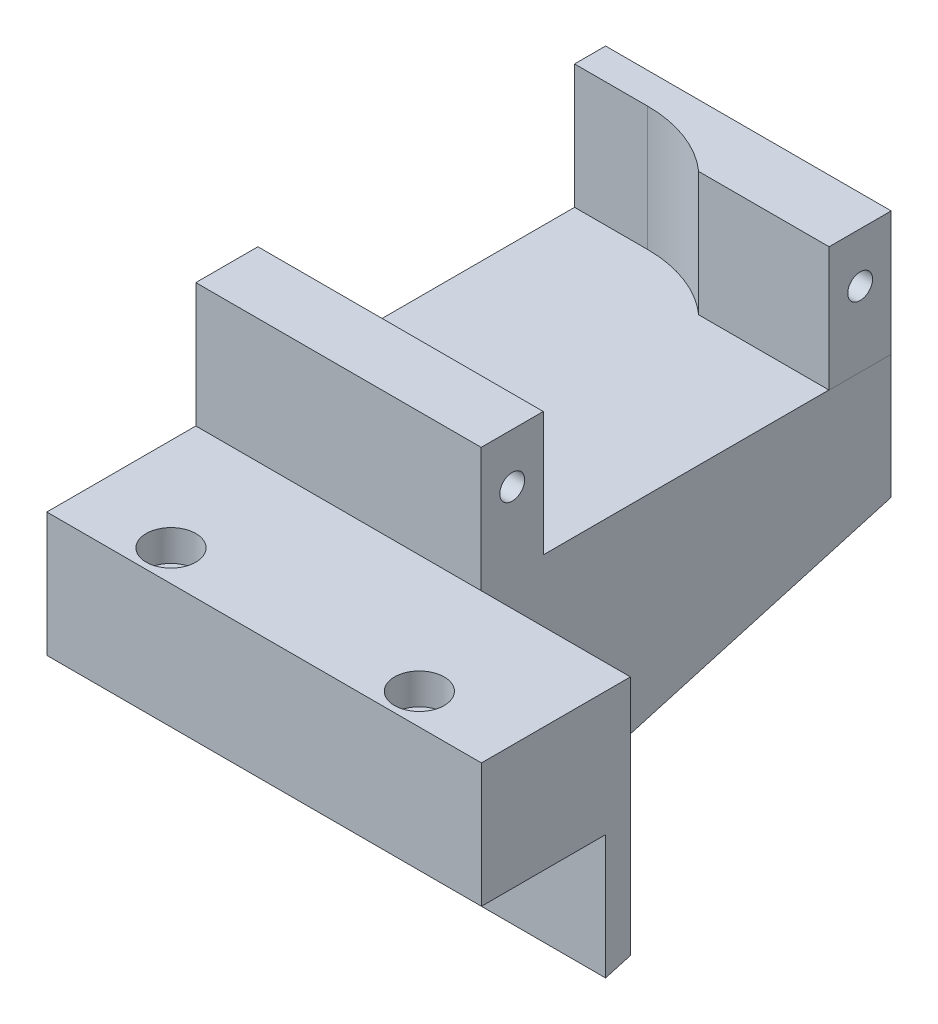
SolidWorks part; units mm, degrees
ref_plane "Front Plane" through (0, 0, 0) normal (0, 0, 1) x (1, 0, 0)
ref_plane "Top Plane" through (0, 0, 0) normal (0, 1, 0) x (1, 0, 0)
ref_plane "Right Plane" through (0, 0, 0) normal (1, 0, 0) x (0, 0, -1)
sketch "Sketch1" plane through (0, 0, 0) normal (0, 1, 0) x (1, 0, 0)
  line L1 (-17.5, 40) -> (17.5, 40)
  line L2 (-17.5, 40) -> (-17.5, -5)
  line L3 (-17.5, -5) -> (17.5, -5)
  line L4 (17.5, 40) -> (17.5, -5)
  circle A0 centre (-10, -2.5) radius 1.1
  circle A1 centre (10, -2.5) radius 1.1
  point P0 (0, 0)
  point P9 (0, 0)
  dimension "D1" = 20
  dimension "D2" = 2.5
extrude "Boss-Extrude1" add sketch "Sketch1" along normal blind 10
sketch "Sketch5" plane through (0, 0, 0) normal (0, -1, 0) x (1, 0, 0)
  line L0 (17.5, 5) -> (17.5, -40) construction
  line L1 (-17.5, -40) -> (17.5, -40)
  line L2 (-17.5, -40) -> (-17.5, -5)
  line L3 (-17.5, -5) -> (17.5, -5)
  line L4 (17.5, -40) -> (17.5, -5)
extrude "Boss-Extrude3" add sketch "Sketch5" along normal blind 10
sketch "Sketch6" plane through (17.5, 0, 0) normal (1, 0, 0) x (0, 0, -1)
  line L0 (5, -10) -> (40, 0)
  line L1 (40, 10) -> (40, -10) construction
  line L2 (40, 0) -> (40, -10)
  line L3 (40, -10) -> (5, -10)
extrude "Cut-Extrude1" cut sketch "Sketch6" against normal blind 50
sketch "Sketch7" plane through (0, 10, 0) normal (0, 1, 0) x (1, 0, 0)
  line L1 (-17.5, 40) -> (5.5, 40)
  line L2 (-17.5, 40) -> (-17.5, 35)
  line L3 (-17.5, 35) -> (5.5, 35)
  line L4 (5.5, 40) -> (5.5, 35)
extrude "Boss-Extrude4" add sketch "Sketch7" along normal blind 10
sketch "Sketch8" plane through (0, 10, 0) normal (0, 1, 0) x (1, 0, 0)
  line L5 (-17.5, 12) -> (5.4812, 12)
  line L6 (-17.5, 12) -> (-17.5, 7)
  line L7 (-17.5, 7) -> (5.4812, 7)
  line L8 (5.4812, 12) -> (5.4812, 7)
extrude "Boss-Extrude5" add sketch "Sketch8" along normal blind 10
sketch "Sketch9" plane through (0, 10, 0) normal (0, 1, 0) x (1, 0, 0)
  line L1 (5.4812, 7) -> (17.5, 7)
  line L2 (5.4812, 7) -> (5.4812, 40)
  line L3 (5.4812, 40) -> (17.5, 40)
  line L4 (17.5, 7) -> (17.5, 40)
extrude "Cut-Extrude2" cut sketch "Sketch9" against normal blind 40
sketch "Sketch10" plane through (5.4812, 0, 0) normal (1, 0, 0) x (0, 0, -1)
  line L0 (9.5, 20) -> (9.5, 16)
  line L1 (7, 20) -> (12, 20) construction
  circle A0 centre (9.5, 16) radius 1
sketch "Sketch11" plane through (5.5, 0, 0) normal (1, 0, 0) x (0, 0, -1)
  line L0 (37.5, 20) -> (37.5, 16)
  line L1 (35, 20) -> (40, 20) construction
  circle A0 centre (37.5, 16) radius 1
extrude "Cut-Extrude3" cut sketch "Sketch10" against normal blind 10 contours A0 region at (5.4812, 15.3129, -8.8129)
extrude "Cut-Extrude4" cut sketch "Sketch11" against normal blind 10 contours A0 region at (5.5, 15.3129, -36.8129)
sketch "Sketch13" plane through (-17.5, 0, 0) normal (-1, 0, 0) x (0, 0, 1)
  line L0 (-40, 20) -> (-35, 20) construction
  line L1 (-35, 10) -> (-37.5, 10)
  line L2 (-35, 10) -> (-35, 20)
  line L3 (-35, 20) -> (-37.5, 20)
  line L4 (-37.5, 10) -> (-37.5, 20)
extrude "Cut-Extrude6" cut sketch "Sketch13" against normal blind 12.5
fillet "Fillet1" radius 10 1 edges at (-5, 15, -37.5)
sketch "Sketch14" plane through (0, 10, 0) normal (0, 1, 0) x (1, 0, 0)
  circle A0 centre (10, -2.5) radius 2
  circle A1 centre (-10, -2.5) radius 2
extrude "Cut-Extrude7" cut sketch "Sketch14" against normal blind 2.5
